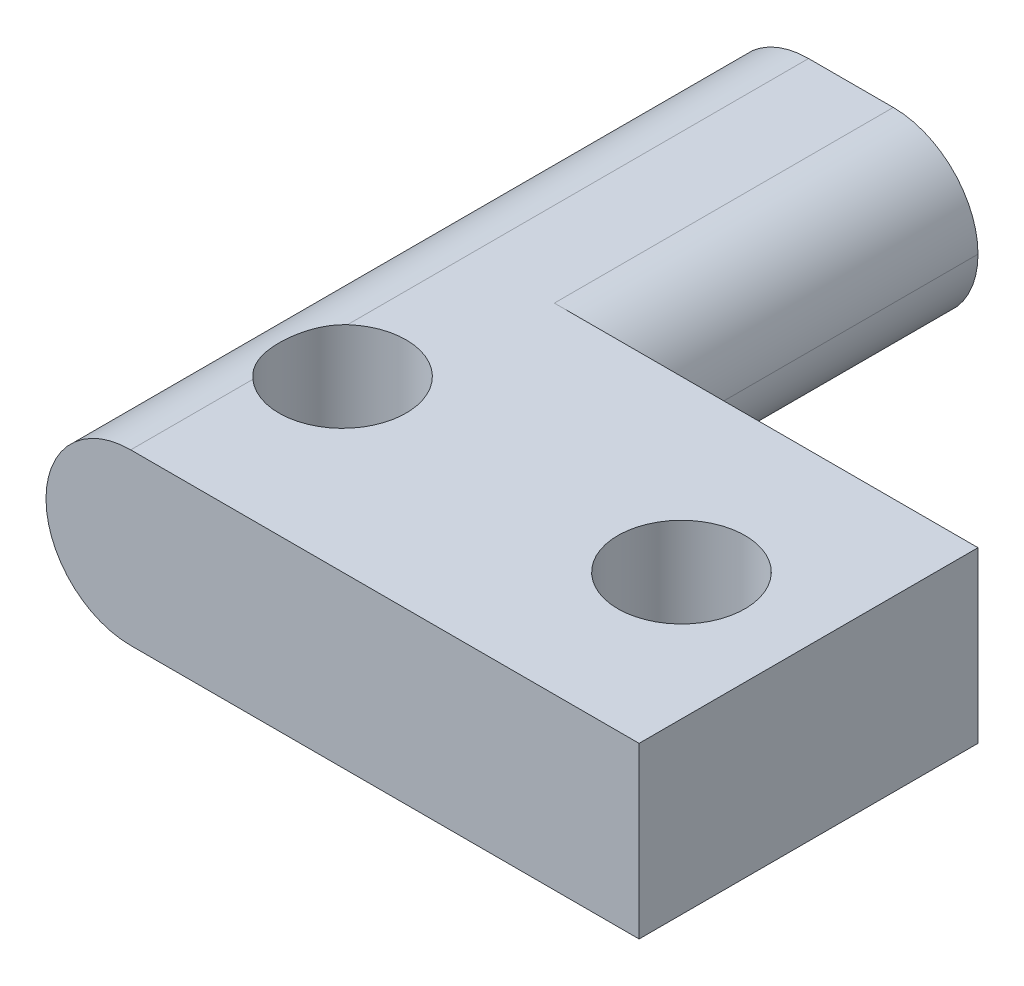
SolidWorks part; units mm, degrees
ref_plane "Front Plane" through (0, 0, 0) normal (0, 0, 1) x (1, 0, 0)
ref_plane "Top Plane" through (0, 0, 0) normal (0, 1, 0) x (1, 0, 0)
ref_plane "Right Plane" through (0, 0, 0) normal (1, 0, 0) x (0, 0, -1)
sketch "Sketch1" plane through (0, 0, 0) normal (0, 1, 0) x (1, 0, 0)
  line L1 (1.5, -4) -> (-1.5, -4)
  line L2 (1.5, -4) -> (1.5, 4)
  line L3 (1.5, 4) -> (-1.5, 4)
  line L4 (-1.5, -4) -> (-1.5, 4)
  line L5 (1.5, -4) -> (-1.5, 4) construction
  line L6 (1.5, 4) -> (-1.5, -4) construction
  circle A0 centre (0, -2) radius 0.75
  point P0 (0, 0)
  dimension "D3" = 1.5
  dimension "D1" = 3
  dimension "D2" = 8
  dimension "D4" = 2
extrude "Boss-Extrude1" add sketch "Sketch1" along normal blind 2
sketch "Sketch2" plane through (1.5, 0, 0) normal (1, 0, 0) x (0, 0, -1)
  line L0 (-4, 0) -> (4, 0) construction
  line L1 (-4, 2) -> (0, 2)
  line L2 (-4, 2) -> (-4, 0)
  line L3 (-4, 0) -> (0, 0)
  line L4 (0, 2) -> (0, 0)
  dimension "D1" = 4
extrude "Boss-Extrude2" add sketch "Sketch2" along normal blind 4
sketch "Sketch3" plane through (0, 2, 0) normal (0, 1, 0) x (1, 0, 0)
  line L0 (0, -2) -> (1.491, -2) construction
  circle A0 centre (4, -2) radius 0.75
  circle A1 centre (0, -2) radius 0.75 construction
  point P4 (0, 0)
  dimension "D1" = 1.5
  dimension "D2" = 4
extrude "Cut-Extrude1" cut sketch "Sketch3" against normal up to next
fillet "Fillet3" radius 1 4 edges at (1.5, 0, -2) (1.5, 2, -2) (-1.5, 0, 0) (-1.5, 2, 0)
